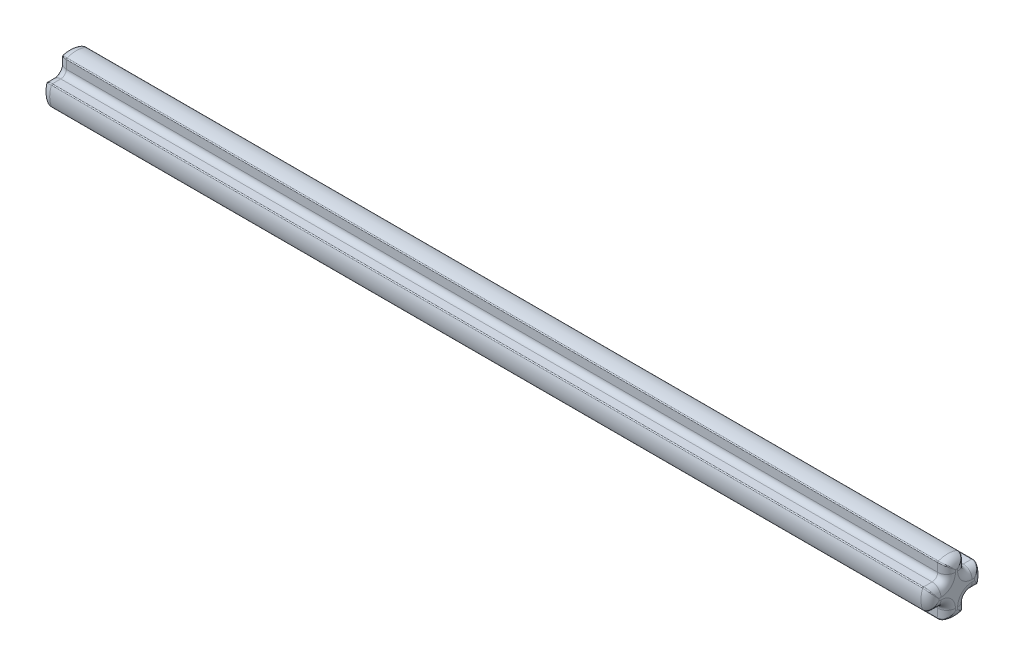
SolidWorks part; units mm, degrees
material "PET"
ref_plane "Alzado" through (0, 0, 0) normal (0, 0, 1) x (1, 0, 0)
ref_plane "Planta" through (0, 0, 0) normal (0, 1, 0) x (1, 0, 0)
ref_plane "Vista lateral" through (0, 0, 0) normal (1, 0, 0) x (0, 0, -1)
sketch "Croquis1" plane through (0, 0, 0) normal (1, 0, 0) x (0, 0, -1)
  line B0 (-1.4, 0.9) -> (-2.1564, 0.9)
  line B1 (0.9, -2.1564) -> (0.9, -1.4)
  line B2 (-0.9, -2.1564) -> (-0.9, -1.4)
  line B3 (2.1564, 0.9) -> (1.4, 0.9)
  line B4 (2.1564, -0.9) -> (1.4, -0.9)
  line B5 (-0.9, 1.4) -> (-0.9, 2.1564)
  line B6 (0.9, 1.4) -> (0.9, 2.1564)
  line B7 (-1.4, -0.9) -> (-2.1564, -0.9)
  arc B8 (-2.2501, 0.8348) -> (-2.2501, -0.8348) centre (0, 0) ccw
  arc B9 (-1.4, -0.9) -> (-0.9, -1.4) centre (-1.4, -1.4) cw
  arc B10 (0.9, -1.4) -> (1.4, -0.9) centre (1.4, -1.4) cw
  arc B11 (1.4, 0.9) -> (0.9, 1.4) centre (1.4, 1.4) cw
  arc B12 (-0.9, 1.4) -> (-1.4, 0.9) centre (-1.4, 1.4) cw
  arc B13 (0.8348, 2.2501) -> (-0.8348, 2.2501) centre (0, 0) ccw
  arc B14 (2.2501, -0.8348) -> (2.2501, 0.8348) centre (0, 0) ccw
  arc B15 (-0.8348, -2.2501) -> (0.8348, -2.2501) centre (0, 0) ccw
  arc B16 (-0.8348, 2.2501) -> (-0.9, 2.1564) centre (-0.8, 2.1564) ccw
  arc B17 (0.8348, 2.2501) -> (0.9, 2.1564) centre (0.8, 2.1564) cw
  arc B18 (2.2501, 0.8348) -> (2.1564, 0.9) centre (2.1564, 0.8) ccw
  arc B19 (2.2501, -0.8348) -> (2.1564, -0.9) centre (2.1564, -0.8) cw
  arc B20 (0.9, -2.1564) -> (0.8348, -2.2501) centre (0.8, -2.1564) cw
  arc B21 (-0.8348, -2.2501) -> (-0.9, -2.1564) centre (-0.8, -2.1564) cw
  arc B22 (-2.1564, -0.9) -> (-2.2501, -0.8348) centre (-2.1564, -0.8) cw
  arc B23 (-2.1564, 0.9) -> (-2.2501, 0.8348) centre (-2.1564, 0.8) ccw
sketch_block_instance "Axle Section Block Rounded 0.1 mm-1"
sketch_block "Axle Section Block Rounded 0.1 mm" parameters "D1"=4.8, "D3"=0.5, "D4"=0.1, "D2"=1.8
extrude "Saliente-Extruir1" add sketch "Croquis1" along normal blind 80
fillet "Redondeo1" radius 0.8 48 edges at (0, 1.7782, 0.9) (0, 1.0464, 1.0464) (0, 0.9, 1.7782) (0, 0.8821, 2.2135) (0, 0, 2.4) (0, -0.8821, 2.2135) (0, -0.9, 1.7782) (0, -1.0464, 1.0464) (0, -1.7782, 0.9) (0, -2.2135, 0.8821) (0, -2.4, 0) (0, -2.2135, -0.8821) (0, -1.7782, -0.9) (0, -1.0464, -1.0464) (0, -0.9, -1.7782) (0, -0.8821, -2.2135) (0, 0, -2.4) (0, 0.8821, -2.2135) (0, 0.9, -1.7782) (0, 1.0464, -1.0464) (0, 1.7782, -0.9) (0, 2.2135, -0.8821) (0, 2.4, 0) (0, 2.2135, 0.8821) (80, 2.4, 0) (80, 2.2135, -0.8821) (80, 1.7782, -0.9) (80, 1.0464, -1.0464) (80, 0.9, -1.7782) (80, 0.8821, -2.2135) (80, 0, -2.4) (80, -0.8821, -2.2135) (80, -0.9, -1.7782) (80, -1.0464, -1.0464) (80, -1.7782, -0.9) (80, -2.2135, -0.8821) (80, -2.4, 0) (80, -2.2135, 0.8821) (80, -1.7782, 0.9) (80, -1.0464, 1.0464) (80, -0.9, 1.7782) (80, -0.8821, 2.2135) (80, 0, 2.4) (80, 0.8821, 2.2135) (80, 0.9, 1.7782) (80, 1.0464, 1.0464) (80, 1.7782, 0.9) (80, 2.2135, 0.8821)
